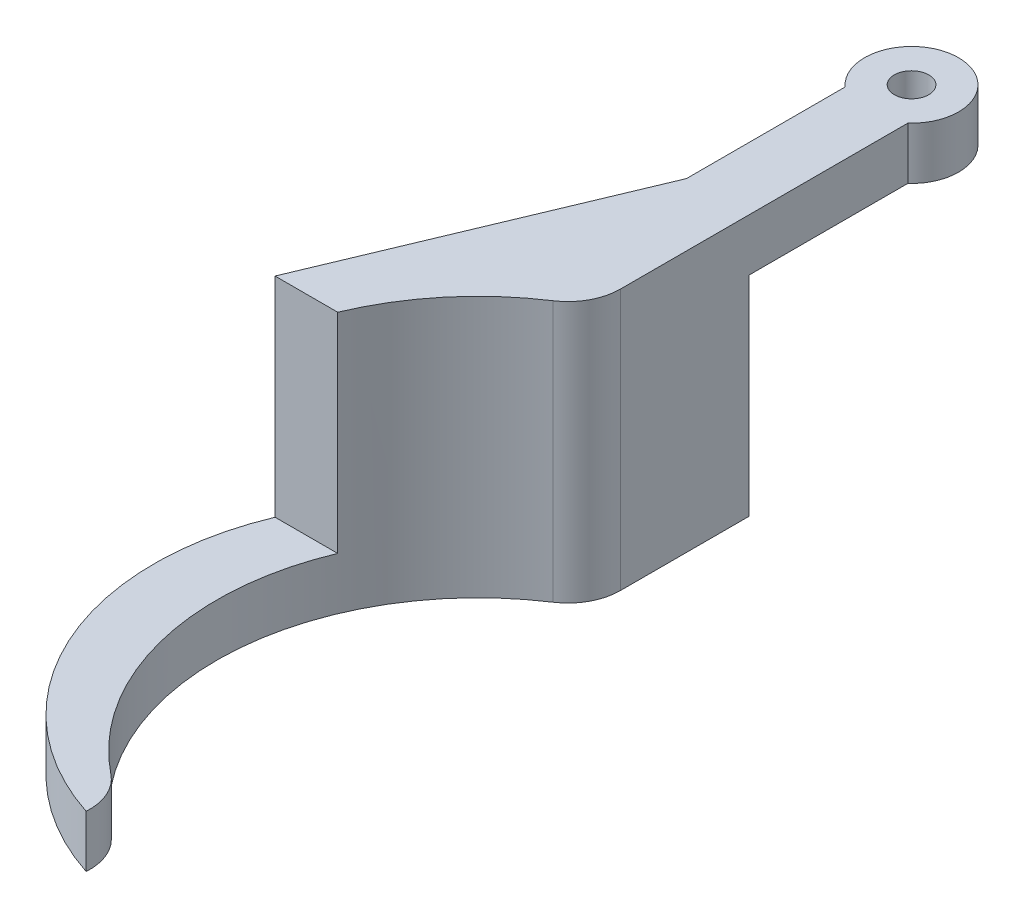
SolidWorks part; units mm, degrees
ref_plane "前视基准面" through (0, 0, 0) normal (0, 0, 1) x (1, 0, 0)
ref_plane "上视基准面" through (0, 0, 0) normal (0, 1, 0) x (1, 0, 0)
ref_plane "右视基准面" through (0, 0, 0) normal (1, 0, 0) x (0, 0, -1)
other "Configuration Table"
sketch "草图3" plane through (0, 0, 0) normal (0, 1, 0) x (1, 0, 0)
  line L0 (0, 0) -> (0, -9.9636) construction
  line L1 (-3, -3.3541) -> (3, -3.3541) construction
  line L2 (-3, -3.3541) -> (-3, -7.4162)
  line L3 (3, -3.3541) -> (3, -7.4162)
  line L7 (3, -7.4162) -> (3, -10.583)
  line L10 (-3, -43.8541) -> (3, -43.8541)
  line L11 (3, -43.8541) -> (3, -10.583)
  line L13 (-3, -7.4162) -> (-3, -43.8541)
  arc A0 (3, -3.3541) -> (-3, -3.3541) centre (0, 0) ccw
  point P6 (0, -3.3541)
  dimension "D1" = 9
  dimension "D2" = 6
  dimension "16.66" = 40.5
extrude "凸台-拉伸2" add sketch "草图3" along normal blind 5
sketch "草图4" plane through (0, 5, 0) normal (0, 1, 0) x (1, 0, 0)
  circle A0 centre (0, 0) radius 1.65
  dimension "D1" = 3.3
extrude "切除-拉伸1" cut sketch "草图4" against normal up to surface (5 mm away) up to face at (0, 0, 21.6406)
sketch "草图6" plane through (0, 5, 0) normal (0, 1, 0) x (1, 0, 0)
  line L0 (14.4495, -55.9701) -> (14.4495, -20.0301) construction
  line L1 (14.4495, -55.9701) -> (3, -43.8541) construction
  line L2 (3, -68.0861) -> (0.6636, -72.1328) construction
  line L3 (3, -43.8541) -> (-3, -43.8541) construction
  line L4 (3, -43.8541) -> (3, -33.746) construction
  line L5 (3, -43.8541) -> (3, -3.3541) construction
  line L6 (3, -33.746) -> (-3, -33.746)
  line L7 (-3, -3.3541) -> (-3, -43.8541) construction
  line L8 (14.4495, -55.9701) -> (1.9495, -77.6207) construction
  line L9 (1.9495, -77.6207) -> (0.7225, -79.746)
  arc A0 (3, -43.8541) -> (3, -68.0861) centre (14.4495, -55.9701) ccw construction
  arc A1 (-3, -43.8541) -> (0.6636, -72.1328) centre (14.4495, -55.9701) ccw construction
  arc A4 (3, -33.746) -> (1.9495, -77.6207) centre (14.4495, -55.9701) ccw
  arc A5 (-3, -33.746) -> (0.7225, -79.746) centre (8.4495, -55.9701) ccw
  dimension "D1" = 33.34
  dimension "D3" = 30
  dimension "D4" = 30
  dimension "D2" = 43.38
extrude "凸台-拉伸3" add sketch "草图6" against normal blind 5
sketch "草图7" plane through (0, 5, 0) normal (0, 1, 0) x (1, 0, 0)
  circle A0 centre (0, 0) radius 3
  dimension "D1" = 6
extrude "切除-拉伸2" cut sketch "草图7" against normal blind 3 from offset 4.5 offset against normal yes
sketch "草图8" plane through (0, 5, 0) normal (0, 1, 0) x (1, 0, 0)
  line L0 (-3, -38.0672) -> (-3, -43.8541)
  line L1 (-3, -43.8541) -> (3, -43.8541)
  line L2 (3, -43.8541) -> (3, -33.746)
  line L3 (3, -43.8541) -> (3, -3.3541) construction
  arc A0 (3, -33.746) -> (-3, -38.0672) centre (14.4495, -55.9701) ccw
extrude "切除-拉伸3" cut sketch "草图8" against normal blind 7.5
sketch "草图9" plane through (0, 5, 0) normal (0, 1, 0) x (1, 0, 0)
  line L0 (-3, -18.5501) -> (-14.615, -46.3249)
  line L1 (-3, -3.3541) -> (-3, -33.746) construction
  line L2 (-3, -18.5501) -> (-3, -33.746)
  arc A0 (-3, -33.746) -> (0.7225, -79.746) centre (8.4495, -55.9701) ccw construction
  arc A1 (-3, -33.746) -> (-14.615, -46.3249) centre (8.4495, -55.9701) ccw
extrude "凸台-拉伸4" add sketch "草图9" against normal blind 5
fillet "圆角1" radius 5 1 edges at (3, 2.5, 33.746)
fillet "圆角2" radius 5 1 edges at (1.9495, 2.5, 77.6207)
sketch "草图10" plane through (0, 0, 0) normal (0, -1, 0) x (1, 0, 0)
  line L0 (-3, 18.5501) -> (3, 18.5501)
  line L1 (-14.615, 46.3249) -> (-8.615, 46.3249)
  line L3 (-14.615, 46.3249) -> (-3, 18.5501)
  line L4 (-3, 18.5501) -> (-3, 3.3541)
  line L5 (3, 3.3541) -> (3, 30.882)
  line L6 (-14.615, 46.3249) -> (-3, 18.5501)
  line L8 (3, 18.5501) -> (3, 30.882)
  arc A5 (-1.1472, 75.5083) -> (0.7416, 35.0633) centre (14.4495, 55.9701) ccw
  arc A6 (-1.1472, 75.5083) -> (0.7225, 79.746) centre (-4.2666, 79.4159) ccw
  arc A7 (0.7225, 79.746) -> (-14.615, 46.3249) centre (8.4495, 55.9701) ccw
  arc A8 (-3, 3.3541) -> (3, 3.3541) centre (0, 0) ccw
  arc A9 (3, 30.882) -> (0.7416, 35.0633) centre (-2, 30.882) ccw
  arc A10 (-8.615, 46.3249) -> (0.7416, 35.0633) centre (14.4495, 55.9701) ccw
  arc A14 (3, 30.882) -> (0.7416, 35.0633) centre (-2, 30.882) ccw
  dimension "D1" = 0
extrude "凸台-拉伸5" add sketch "草图10" along normal blind 15
sketch "草图11" plane through (0, -15, 0) normal (0, -1, 0) x (1, 0, 0)
  line L1 (-14.615, 46.3249) -> (-8.615, 46.3249)
  line L6 (-8.615, 46.3249) -> (-14.615, 46.3249)
  line L7 (-14.615, 46.3249) -> (-3, 18.5501)
  line L8 (-3, 18.5501) -> (3, 18.5501)
  line L9 (3, 18.5501) -> (3, 30.882)
  line L11 (-14.615, 46.3249) -> (-3, 18.5501)
  line L12 (-3, 18.5501) -> (3, 18.5501)
  line L13 (3, 18.5501) -> (3, 30.882)
  arc A2 (3, 30.882) -> (0.7416, 35.0633) centre (-2, 30.882) ccw
  arc A3 (-1.1472, 75.5083) -> (-8.615, 46.3249) centre (14.4495, 55.9701) ccw
  arc A4 (-1.1472, 75.5083) -> (0.7225, 79.746) centre (-4.2666, 79.4159) ccw
  arc A5 (0.7225, 79.746) -> (-14.615, 46.3249) centre (8.4495, 55.9701) ccw
  arc A6 (-1.1472, 75.5083) -> (-8.615, 46.3249) centre (14.4495, 55.9701) ccw
  arc A7 (-1.1472, 75.5083) -> (0.7225, 79.746) centre (-4.2666, 79.4159) ccw
  arc A8 (0.7225, 79.746) -> (-14.615, 46.3249) centre (8.4495, 55.9701) ccw
  arc A9 (-8.615, 46.3249) -> (0.7416, 35.0633) centre (14.4495, 55.9701) ccw
  arc A10 (3, 30.882) -> (0.7416, 35.0633) centre (-2, 30.882) ccw
  arc A11 (-8.615, 46.3249) -> (0.7416, 35.0633) centre (14.4495, 55.9701) ccw
  dimension "D1" = 0
  dimension "D2" = 0
extrude "凸台-拉伸6" add sketch "草图11" along normal blind 5
sketch "草图12" plane through (0, 0, 0) normal (0, -1, 0) x (1, 0, 0)
  line L1 (-14.615, 46.3249) -> (-8.615, 46.3249)
  line L2 (-14.615, 46.3249) -> (-8.615, 46.3249)
  arc A3 (-1.1472, 75.5083) -> (-8.615, 46.3249) centre (14.4495, 55.9701) ccw
  arc A4 (-1.1472, 75.5083) -> (0.7225, 79.746) centre (-4.2666, 79.4159) ccw
  arc A5 (0.7225, 79.746) -> (-14.615, 46.3249) centre (8.4495, 55.9701) ccw
  arc A6 (-1.1472, 75.5083) -> (-8.615, 46.3249) centre (14.4495, 55.9701) ccw
  arc A7 (-1.1472, 75.5083) -> (0.7225, 79.746) centre (-4.2666, 79.4159) ccw
  arc A8 (0.7225, 79.746) -> (-14.615, 46.3249) centre (8.4495, 55.9701) ccw
  dimension "D1" = 0
extrude "切除-拉伸4" cut sketch "草图12" against normal blind 5
